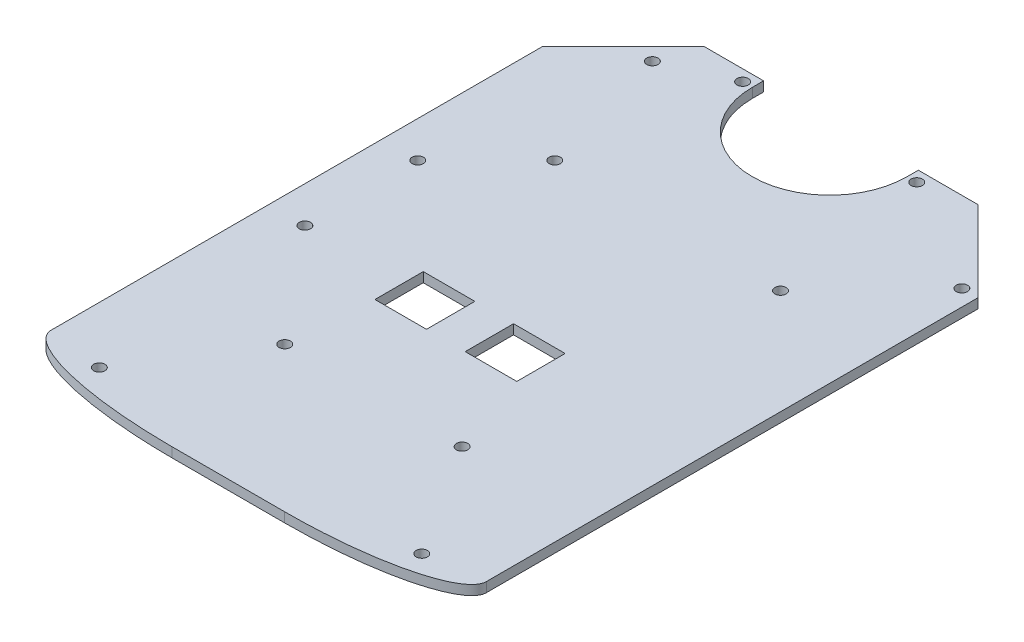
SolidWorks part; units mm, degrees
material "Balsa"
ref_plane "Alzado" through (0, 0, 0) normal (0, 0, 1) x (1, 0, 0)
ref_plane "Planta" through (0, 0, 0) normal (0, 1, 0) x (1, 0, 0)
ref_plane "Vista lateral" through (0, 0, 0) normal (1, 0, 0) x (0, 0, -1)
sketch "Sketch2" plane through (0, 0, 0) normal (0, 1, 0) x (1, 0, 0)
  line L1 (-67.5, 95) -> (67.5, 95)
  line L2 (-67.5, 95) -> (-67.5, -95)
  line L3 (-67.5, -95) -> (67.5, -95)
  line L4 (67.5, 95) -> (67.5, -95)
  line L5 (-67.5, 95) -> (67.5, -95) construction
  line L6 (-67.5, -95) -> (67.5, 95) construction
  point P0 (0, 0)
  dimension "D1" = 135
  dimension "D2" = 190
extrude "Boss-Extrude2" add sketch "Sketch2" along normal blind 3
sketch "Sketch3" plane through (0, 3, 0) normal (0, 1, 0) x (1, 0, 0)
  line L0 (0, -95) -> (0, 95) construction
  line L1 (-67.5, -95) -> (67.5, -95) construction
  line L2 (67.5, 95) -> (-67.5, 95) construction
  line L3 (-67.5, 95) -> (-67.5, -95) construction
  line L4 (-67.5, -95) -> (67.5, -95) construction
  circle A0 centre (-27.5, -50) radius 1.75
  circle A1 centre (27.5, -50) radius 1.75
  circle A2 centre (-50, -85) radius 1.75
  circle A3 centre (50, -85) radius 1.75
  dimension "D1" = 40
  dimension "D3" = 3.5
  dimension "D4" = 10
  dimension "D2" = 45
  dimension "D5" = 50
extrude "Cut-Extrude1" cut sketch "Sketch3" against normal through all
fillet "Fillet1" radius 12.5 1 edges at (-67.5, 1.5, 95) second distance 50 first distance on face at (-67.5, 1.5, 0)
fillet "Fillet2" radius 12.5 1 edges at (67.5, 1.5, 95) second distance 50 first distance on face at (67.5, 1.5, 0)
chamfer "Chamfer2" distance 25 angle 45 1 edges at (67.5, 1.5, -95)
chamfer "Chamfer3" distance 25 angle 45 1 edges at (-67.5, 1.5, -95)
sketch "Sketch7" plane through (0, 3, 0) normal (0, 1, 0) x (1, 0, 0)
  line L0 (42.5, 95) -> (-42.5, 95) construction
  line L1 (24, 91.5) -> (24, 95)
  line L2 (24, 95) -> (-24, 95)
  line L3 (-24, 95) -> (-24, 91.5)
  arc A0 (-24, 91.5) -> (24, 91.5) centre (0, 91.5) ccw
  dimension "D2" = 48
  dimension "D1" = 3.5
extrude "Cut-Extrude5" cut sketch "Sketch7" against normal through all
sketch "Sketch8" plane through (0, 3, 0) normal (0, 1, 0) x (1, 0, 0)
  line L0 (-27, 91.5) -> (27, 91.5) construction
  line L1 (-24, 95) -> (-42.5, 95) construction
  line L2 (-24, 95) -> (24, 95) construction
  line L3 (0, -95) -> (0, 95) construction
  line L4 (-17.5, -95) -> (17.5, -95) construction
  circle A0 centre (-27, 91.5) radius 1.75
  circle A1 centre (27, 91.5) radius 1.75
  point P14 (0, 91.5)
  dimension "D1" = 3.5
  dimension "D2" = 3.5
  dimension "D3" = 54
extrude "Cut-Extrude6" cut sketch "Sketch8" against normal through all
sketch "Sketch9" plane through (0, 3, 0) normal (0, 1, 0) x (1, 0, 0)
  line L0 (-17.5, -95) -> (17.5, -95) construction
  line L1 (0, -95) -> (0, 67.5) construction
  line L2 (-56.25, 20) -> (-56.25, -15) construction
  line L4 (-67.5, 70) -> (-67.5, -82.5) construction
  circle A0 centre (-56.25, -15) radius 1.75
  circle A1 centre (-35, 41.25) radius 1.75
  arc A3 (-24, 91.5) -> (24, 91.5) centre (0, 91.5) ccw construction
  circle A4 centre (-56.25, 20) radius 1.75
  circle A5 centre (35, 41.25) radius 1.75
  dimension "D1" = 3.5
  dimension "D2" = 80
  dimension "D3" = 56.25
  dimension "D4" = 35
  dimension "D5" = 21.25
  dimension "D6" = 21.25
extrude "Cut-Extrude7" cut sketch "Sketch9" against normal through all
sketch "Sketch11" plane through (0, 3, 0) normal (0, 1, 0) x (1, 0, 0)
  line L0 (42.5, 95) -> (24, 95) construction
  line L1 (67.5, -82.5) -> (67.5, 70) construction
  line L4 (-24, 95) -> (-42.5, 95) construction
  circle A0 centre (62.5, 70) radius 1.75
  circle A2 centre (-46.5, 83) radius 1.75
  dimension "D3" = 3.5
  dimension "D1" = 25
  dimension "D2" = 5
  dimension "D4" = 12
  dimension "D5" = 4
extrude "Cut-Extrude8" cut sketch "Sketch11" against normal through all
sketch "Sketch12" plane through (0, 3, 0) normal (0, 1, 0) x (1, 0, 0)
  line L0 (-17.5, -95) -> (17.5, -95) construction
  line L1 (-25.535, -9) -> (-9.535, -9)
  line L2 (-25.535, -9) -> (-25.535, -24)
  line L3 (-25.535, -24) -> (-9.535, -24)
  line L4 (-9.535, -9) -> (-9.535, -24)
  line L5 (2.465, -9) -> (18.465, -9)
  line L6 (2.465, -9) -> (2.465, -24)
  line L7 (2.465, -24) -> (18.465, -24)
  line L8 (18.465, -9) -> (18.465, -24)
  dimension "D1" = 71
  dimension "D2" = 16
  dimension "D3" = 12
  dimension "D4" = 8.035
  dimension "D5" = 15
extrude "Cut-Extrude9" cut sketch "Sketch12" against normal through all
